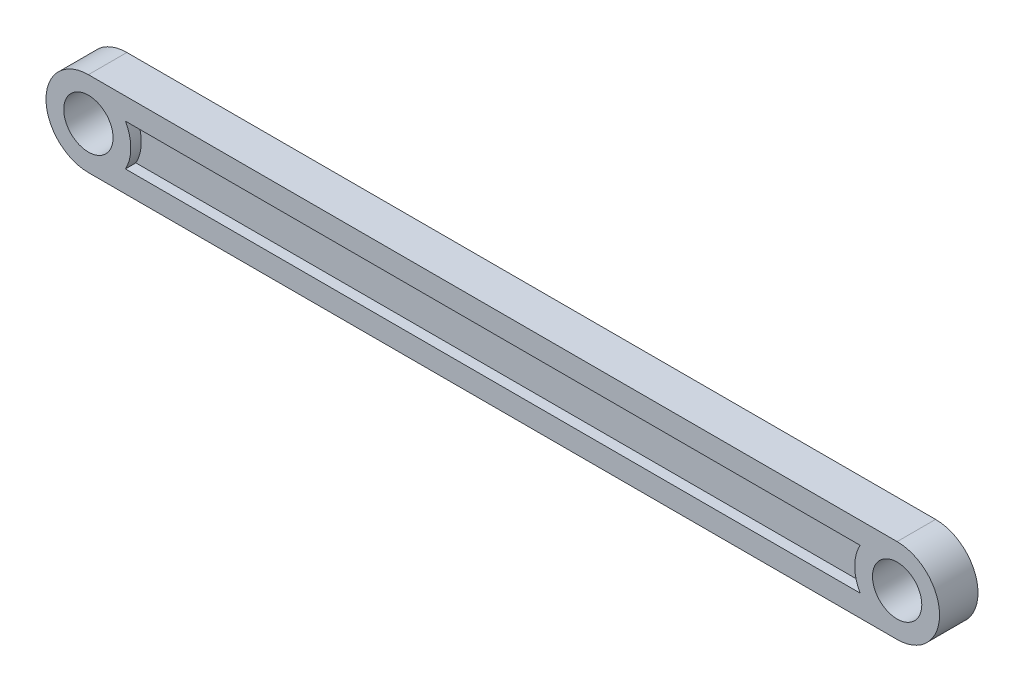
SolidWorks part; units mm, degrees
ref_plane "Front Plane" through (0, 0, 0) normal (0, 0, 1) x (1, 0, 0)
ref_plane "Top Plane" through (0, 0, 0) normal (0, 1, 0) x (1, 0, 0)
ref_plane "Right Plane" through (0, 0, 0) normal (1, 0, 0) x (0, 0, -1)
sketch "Sketch1" plane through (0, 0, 0) normal (0, 0, 1) x (1, 0, 0)
  line L0 (41, 0) -> (-41, 0) construction
  line L1 (41, -4.3) -> (-41, -4.3)
  line L2 (41, 4.3) -> (-41, 4.3)
  arc A0 (41, -4.3) -> (41, 4.3) centre (41, 0) ccw
  arc A1 (-41, 4.3) -> (-41, -4.3) centre (-41, 0) ccw
  circle A2 centre (-41, 0) radius 2.5
  circle A3 centre (41, 0) radius 2.5
  point P2 (0, 0)
  dimension "D3" = 5
  dimension "D1" = 8.6
  dimension "D2" = 82
extrude "Boss-Extrude1" add sketch "Sketch1" along normal mid plane 3.9
sketch "Sketch2" plane through (0, 0, 1.95) normal (0, 0, 1) x (1, 0, 0)
  line L0 (41, 2.1) -> (-41, 2.1)
  line L1 (-41, -2.1) -> (41, -2.1)
  line L2 (41, 4.3) -> (-41, 4.3)
  line L3 (-41, -4.3) -> (41, -4.3)
  line L4 (41, 4.3) -> (-41, 4.3)
  line L5 (-41, -4.3) -> (41, -4.3)
  arc A2 (41, -4.3) -> (41, 4.3) centre (41, 0) ccw
  arc A3 (-41, 4.3) -> (-41, -4.3) centre (-41, 0) ccw
  arc A4 (41, -4.3) -> (41, 4.3) centre (41, 0) ccw
  arc A5 (-41, 4.3) -> (-41, -4.3) centre (-41, 0) ccw
  circle A8 centre (-41, 0) radius 4.3
  circle A9 centre (41, 0) radius 4.3
  arc A10 (41, -2.1) -> (41, 2.1) centre (41, 0) ccw
  arc A11 (-41, 2.1) -> (-41, -2.1) centre (-41, 0) ccw
  dimension "D1" = 0
  dimension "D2" = 2.2
extrude "Cut-Extrude1" cut sketch "Sketch2" against normal blind 1.06 contours A9 L0 A8 L1 region at (0, 0, 1.95)
mirror "Mirror1" about plane through (0, 0, 0) normal (0, 0, 1) of "Cut-Extrude1"
